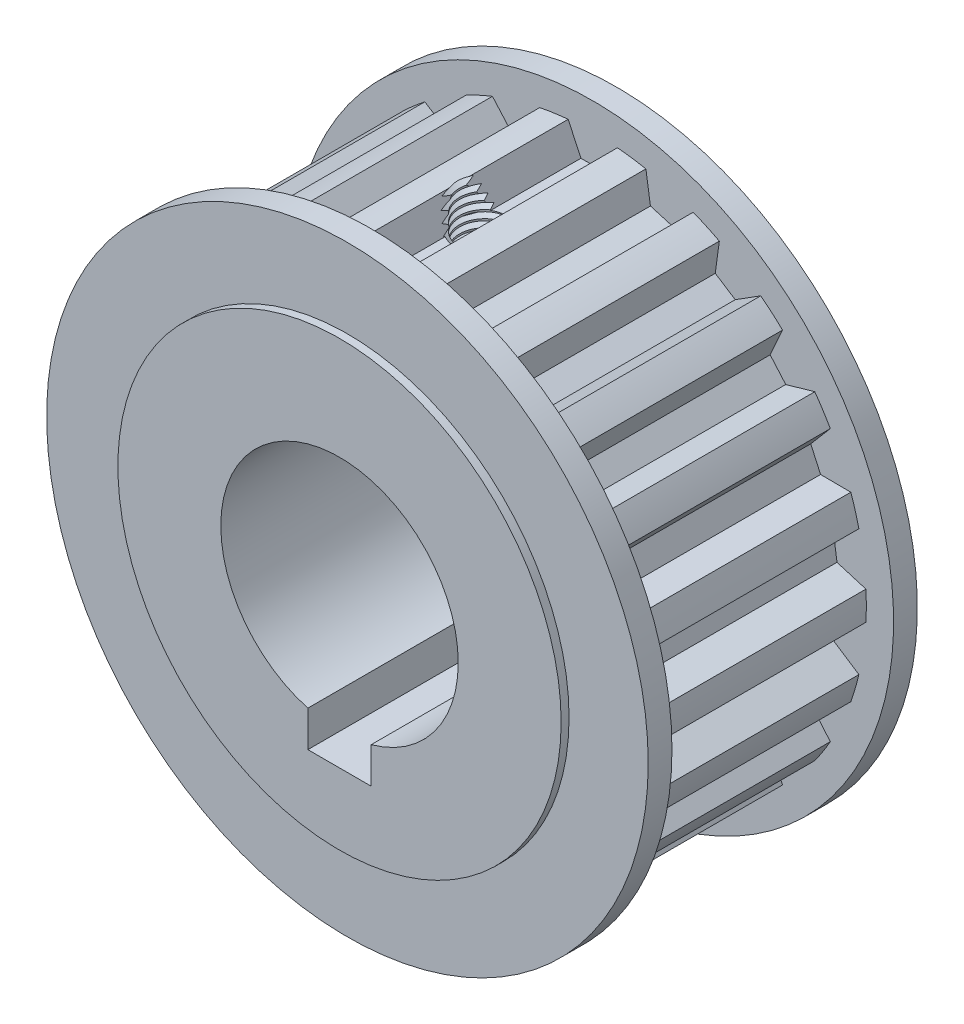
SolidWorks part; units mm, degrees
ref_plane "Front Plane" through (0, 0, 0) normal (0, 0, 1) x (1, 0, 0)
ref_plane "Top Plane" through (0, 0, 0) normal (0, 1, 0) x (1, 0, 0)
ref_plane "Right Plane" through (0, 0, 0) normal (1, 0, 0) x (0, 0, -1)
sketch "Sketch1" plane through (0, 0, 0) normal (0, 0, 1) x (1, 0, 0)
  circle A0 centre (0, 0) radius 17.275
  circle A1 centre (0, 0) radius 7.5
  dimension "D1" = 34.55
  dimension "D2" = 15
extrude "Boss-Extrude1" add sketch "Sketch1" along normal blind 18
sketch "Sketch2" plane through (0, 0, 18) normal (0, 0, 1) x (1, 0, 0)
  line L0 (0, 17.275) -> (0, 15.475) construction
  line L1 (-0.75, 15.475) -> (0.75, 15.475)
  line L2 (0.75, 15.475) -> (1.756, 17.6325)
  line L3 (-0.75, 15.475) -> (-1.756, 17.6325)
  line L4 (-1.756, 17.6325) -> (1.756, 17.6325)
  circle A0 centre (0, 0) radius 17.275 construction
  point P9 (0, 15.475)
  dimension "D1" = 1.8
  dimension "D2" = 1.5
  dimension "D3" = 25
  dimension "D4" = 25
extrude "Cut-Extrude1" cut sketch "Sketch2" against normal blind 18
pattern_circular "CirPattern1" count 22 over 360 about axis through (0, 0, 0) along (0, 0, 1) of "Cut-Extrude1"
sketch "Sketch3" plane through (0, 0, 18) normal (0, 0, 1) x (1, 0, 0)
  circle A0 centre (0, 0) radius 17.275
  circle A1 centre (0, 0) radius 14
extrude "Cut-Extrude2" cut sketch "Sketch3" against normal blind 2
sketch "Sketch4" plane through (0, 0, 0) normal (0, 0, -1) x (-1, 0, 0)
  circle A0 centre (0, 0) radius 17.275
  circle A2 centre (0, 0) radius 14
extrude "Cut-Extrude3" cut sketch "Sketch4" against normal blind 2
sketch "Sketch5" plane through (0, 0, 0) normal (0, 1, 0) x (1, 0, 0)
  line L0 (0, 0) -> (0, -18) construction
  line L1 (-14, -18) -> (14, -18) construction
  circle A0 centre (0, -9) radius 1.5
  dimension "D1" = 3
extrude "Cut-Extrude4" cut sketch "Sketch5" along normal blind 18
sketch "Sketch6" plane through (0, 0, 0) normal (0, 1, 0) x (1, 0, 0)
  line L0 (0, 0) -> (0, -18) construction
  line L1 (-14, -18) -> (14, -18) construction
  circle A0 centre (0, -9) radius 1.5
curve "Helix/Spiral1" pitch 0.5 height 20 turns 40
sketch "Sketch7" plane through (0, 0, 0) normal (1, 0, 0) x (0, 0, -1)
  line L1 (-10.8284, 19.9865) -> (-10.3034, 19.6834)
  line L2 (-10.3034, 19.6834) -> (-10.3034, 20.2896)
  line L3 (-10.3034, 20.2896) -> (-10.8284, 19.9865)
  circle A0 centre (-10.4784, 19.9865) radius 0.175 construction
  spline S0 degree 3 poles (-10.5, 0) (-10.5, 0.0104) (-10.4219, 0.0313) (-10.0883, 0.0625) (-9.589, 0.0938) (-9, 0.125) (-8.411, 0.1563) (-7.9117, 0.1875) (-7.5781, 0.2188) (-7.4609, 0.25) (-7.5781, 0.2813) (-7.9117, 0.3125) (-8.411, 0.3438) (-9, 0.375) (-9.589, 0.4063) (-10.0883, 0.4375) (-10.4219, 0.4688) (-10.5391, 0.5) (-10.4219, 0.5313) (-10.0883, 0.5625) (-9.589, 0.5938) (-9, 0.625) (-8.411, 0.6563) (-7.9117, 0.6875) (-7.5781, 0.7188) (-7.4609, 0.75) (-7.5781, 0.7813) (-7.9117, 0.8125) (-8.411, 0.8438) (-9, 0.875) (-9.589, 0.9063) (-10.0883, 0.9375) (-10.4219, 0.9688) (-10.5391, 1) (-10.4219, 1.0313) (-10.0883, 1.0625) (-9.589, 1.0938) (-9, 1.125) (-8.411, 1.1563) (-7.9117, 1.1875) (-7.5781, 1.2188) (-7.4609, 1.25) (-7.5781, 1.2813) (-7.9117, 1.3125) (-8.411, 1.3438) (-9, 1.375) (-9.589, 1.4063) (-10.0883, 1.4375) (-10.4219, 1.4688) (-10.5391, 1.5) (-10.4219, 1.5313) (-10.0883, 1.5625) (-9.589, 1.5938) (-9, 1.625) (-8.411, 1.6563) (-7.9117, 1.6875) (-7.5781, 1.7188) (-7.4609, 1.75) (-7.5781, 1.7813) (-7.9117, 1.8125) (-8.411, 1.8438) (-9, 1.875) (-9.589, 1.9063) (-10.0883, 1.9375) (-10.4219, 1.9688) (-10.5391, 2) (-10.4219, 2.0313) (-10.0883, 2.0625) (-9.589, 2.0938) (-9, 2.125) (-8.411, 2.1563) (-7.9117, 2.1875) (-7.5781, 2.2188) (-7.4609, 2.25) (-7.5781, 2.2813) (-7.9117, 2.3125) (-8.411, 2.3438) (-9, 2.375) (-9.589, 2.4063) (-10.0883, 2.4375) (-10.4219, 2.4688) (-10.5391, 2.5) (-10.4219, 2.5313) (-10.0883, 2.5625) (-9.589, 2.5938) (-9, 2.625) (-8.411, 2.6563) (-7.9117, 2.6875) (-7.5781, 2.7188) (-7.4609, 2.75) (-7.5781, 2.7813) (-7.9117, 2.8125) (-8.411, 2.8438) (-9, 2.875) (-9.589, 2.9063) (-10.0883, 2.9375) (-10.4219, 2.9688) (-10.5391, 3) (-10.4219, 3.0313) (-10.0883, 3.0625) (-9.589, 3.0938) (-9, 3.125) (-8.411, 3.1563) (-7.9117, 3.1875) (-7.5781, 3.2188) (-7.4609, 3.25) (-7.5781, 3.2813) (-7.9117, 3.3125) (-8.411, 3.3438) (-9, 3.375) (-9.589, 3.4063) (-10.0883, 3.4375) (-10.4219, 3.4688) (-10.5391, 3.5) (-10.4219, 3.5313) (-10.0883, 3.5625) (-9.589, 3.5938) (-9, 3.625) (-8.411, 3.6563) (-7.9117, 3.6875) (-7.5781, 3.7188) (-7.4609, 3.75) (-7.5781, 3.7813) (-7.9117, 3.8125) (-8.411, 3.8438) (-9, 3.875) (-9.589, 3.9063) (-10.0883, 3.9375) (-10.4219, 3.9688) (-10.5391, 4) (-10.4219, 4.0313) (-10.0883, 4.0625) (-9.589, 4.0938) (-9, 4.125) (-8.411, 4.1563) (-7.9117, 4.1875) (-7.5781, 4.2188) (-7.4609, 4.25) (-7.5781, 4.2813) (-7.9117, 4.3125) (-8.411, 4.3438) (-9, 4.375) (-9.589, 4.4063) (-10.0883, 4.4375) (-10.4219, 4.4688) (-10.5391, 4.5) (-10.4219, 4.5313) (-10.0883, 4.5625) (-9.589, 4.5938) (-9, 4.625) (-8.411, 4.6563) (-7.9117, 4.6875) (-7.5781, 4.7188) (-7.4609, 4.75) (-7.5781, 4.7813) (-7.9117, 4.8125) (-8.411, 4.8438) (-9, 4.875) (-9.589, 4.9063) (-10.0883, 4.9375) (-10.4219, 4.9688) (-10.5391, 5) (-10.4219, 5.0313) (-10.0883, 5.0625) (-9.589, 5.0938) (-9, 5.125) (-8.411, 5.1563) (-7.9117, 5.1875) (-7.5781, 5.2188) (-7.4609, 5.25) (-7.5781, 5.2813) (-7.9117, 5.3125) (-8.411, 5.3438) (-9, 5.375) (-9.589, 5.4063) (-10.0883, 5.4375) (-10.4219, 5.4688) (-10.5391, 5.5) (-10.4219, 5.5313) (-10.0883, 5.5625) (-9.589, 5.5938) (-9, 5.625) (-8.411, 5.6563) (-7.9117, 5.6875) (-7.5781, 5.7188) (-7.4609, 5.75) (-7.5781, 5.7813) (-7.9117, 5.8125) (-8.411, 5.8438) (-9, 5.875) (-9.589, 5.9063) (-10.0883, 5.9375) (-10.4219, 5.9688) (-10.5391, 6) (-10.4219, 6.0313) (-10.0883, 6.0625) (-9.589, 6.0938) (-9, 6.125) (-8.411, 6.1563) (-7.9117, 6.1875) (-7.5781, 6.2188) (-7.4609, 6.25) (-7.5781, 6.2813) (-7.9117, 6.3125) (-8.411, 6.3438) (-9, 6.375) (-9.589, 6.4063) (-10.0883, 6.4375) (-10.4219, 6.4688) (-10.5391, 6.5) (-10.4219, 6.5313) (-10.0883, 6.5625) (-9.589, 6.5938) (-9, 6.625) (-8.411, 6.6563) (-7.9117, 6.6875) (-7.5781, 6.7188) (-7.4609, 6.75) (-7.5781, 6.7813) (-7.9117, 6.8125) (-8.411, 6.8438) (-9, 6.875) (-9.589, 6.9063) (-10.0883, 6.9375) (-10.4219, 6.9688) (-10.5391, 7) (-10.4219, 7.0313) (-10.0883, 7.0625) (-9.589, 7.0938) (-9, 7.125) (-8.411, 7.1563) (-7.9117, 7.1875) (-7.5781, 7.2188) (-7.4609, 7.25) (-7.5781, 7.2813) (-7.9117, 7.3125) (-8.411, 7.3438) (-9, 7.375) (-9.589, 7.4063) (-10.0883, 7.4375) (-10.4219, 7.4688) (-10.5391, 7.5) (-10.4219, 7.5313) (-10.0883, 7.5625) (-9.589, 7.5938) (-9, 7.625) (-8.411, 7.6563) (-7.9117, 7.6875) (-7.5781, 7.7188) (-7.4609, 7.75) (-7.5781, 7.7813) (-7.9117, 7.8125) (-8.411, 7.8438) (-9, 7.875) (-9.589, 7.9063) (-10.0883, 7.9375) (-10.4219, 7.9688) (-10.5391, 8) (-10.4219, 8.0313) (-10.0883, 8.0625) (-9.589, 8.0938) (-9, 8.125) (-8.411, 8.1563) (-7.9117, 8.1875) (-7.5781, 8.2188) (-7.4609, 8.25) (-7.5781, 8.2813) (-7.9117, 8.3125) (-8.411, 8.3438) (-9, 8.375) (-9.589, 8.4063) (-10.0883, 8.4375) (-10.4219, 8.4688) (-10.5391, 8.5) (-10.4219, 8.5313) (-10.0883, 8.5625) (-9.589, 8.5938) (-9, 8.625) (-8.411, 8.6563) (-7.9117, 8.6875) (-7.5781, 8.7188) (-7.4609, 8.75) (-7.5781, 8.7813) (-7.9117, 8.8125) (-8.411, 8.8438) (-9, 8.875) (-9.589, 8.9063) (-10.0883, 8.9375) (-10.4219, 8.9688) (-10.5391, 9) (-10.4219, 9.0313) (-10.0883, 9.0625) (-9.589, 9.0938) (-9, 9.125) (-8.411, 9.1563) (-7.9117, 9.1875) (-7.5781, 9.2188) (-7.4609, 9.25) (-7.5781, 9.2813) (-7.9117, 9.3125) (-8.411, 9.3438) (-9, 9.375) (-9.589, 9.4063) (-10.0883, 9.4375) (-10.4219, 9.4688) (-10.5391, 9.5) (-10.4219, 9.5313) (-10.0883, 9.5625) (-9.589, 9.5938) (-9, 9.625) (-8.411, 9.6563) (-7.9117, 9.6875) (-7.5781, 9.7188) (-7.4609, 9.75) (-7.5781, 9.7813) (-7.9117, 9.8125) (-8.411, 9.8438) (-9, 9.875) (-9.589, 9.9063) (-10.0883, 9.9375) (-10.4219, 9.9688) (-10.5391, 10) (-10.4219, 10.0313) (-10.0883, 10.0625) (-9.589, 10.0938) (-9, 10.125) (-8.411, 10.1563) (-7.9117, 10.1875) (-7.5781, 10.2188) (-7.4609, 10.25) (-7.5781, 10.2813) (-7.9117, 10.3125) (-8.411, 10.3438) (-9, 10.375) (-9.589, 10.4063) (-10.0883, 10.4375) (-10.4219, 10.4688) (-10.5391, 10.5) (-10.4219, 10.5313) (-10.0883, 10.5625) (-9.589, 10.5938) (-9, 10.625) (-8.411, 10.6563) (-7.9117, 10.6875) (-7.5781, 10.7188) (-7.4609, 10.75) (-7.5781, 10.7813) (-7.9117, 10.8125) (-8.411, 10.8438) (-9, 10.875) (-9.589, 10.9063) (-10.0883, 10.9375) (-10.4219, 10.9688) (-10.5391, 11) (-10.4219, 11.0313) (-10.0883, 11.0625) (-9.589, 11.0938) (-9, 11.125) (-8.411, 11.1563) (-7.9117, 11.1875) (-7.5781, 11.2188) (-7.4609, 11.25) (-7.5781, 11.2813) (-7.9117, 11.3125) (-8.411, 11.3438) (-9, 11.375) (-9.589, 11.4063) (-10.0883, 11.4375) (-10.4219, 11.4688) (-10.5391, 11.5) (-10.4219, 11.5313) (-10.0883, 11.5625) (-9.589, 11.5938) (-9, 11.625) (-8.411, 11.6563) (-7.9117, 11.6875) (-7.5781, 11.7188) (-7.4609, 11.75) (-7.5781, 11.7813) (-7.9117, 11.8125) (-8.411, 11.8438) (-9, 11.875) (-9.589, 11.9063) (-10.0883, 11.9375) (-10.4219, 11.9688) (-10.5391, 12) (-10.4219, 12.0313) (-10.0883, 12.0625) (-9.589, 12.0938) (-9, 12.125) (-8.411, 12.1563) (-7.9117, 12.1875) (-7.5781, 12.2188) (-7.4609, 12.25) (-7.5781, 12.2813) (-7.9117, 12.3125) (-8.411, 12.3438) (-9, 12.375) (-9.589, 12.4063) (-10.0883, 12.4375) (-10.4219, 12.4688) (-10.5391, 12.5) (-10.4219, 12.5313) (-10.0883, 12.5625) (-9.589, 12.5938) (-9, 12.625) (-8.411, 12.6563) (-7.9117, 12.6875) (-7.5781, 12.7188) (-7.4609, 12.75) (-7.5781, 12.7813) (-7.9117, 12.8125) (-8.411, 12.8438) (-9, 12.875) (-9.589, 12.9063) (-10.0883, 12.9375) (-10.4219, 12.9688) (-10.5391, 13) (-10.4219, 13.0313) (-10.0883, 13.0625) (-9.589, 13.0938) (-9, 13.125) (-8.411, 13.1563) (-7.9117, 13.1875) (-7.5781, 13.2188) (-7.4609, 13.25) (-7.5781, 13.2813) (-7.9117, 13.3125) (-8.411, 13.3438) (-9, 13.375) (-9.589, 13.4063) (-10.0883, 13.4375) (-10.4219, 13.4688) (-10.5391, 13.5) (-10.4219, 13.5313) (-10.0883, 13.5625) (-9.589, 13.5938) (-9, 13.625) (-8.411, 13.6563) (-7.9117, 13.6875) (-7.5781, 13.7188) (-7.4609, 13.75) (-7.5781, 13.7813) (-7.9117, 13.8125) (-8.411, 13.8438) (-9, 13.875) (-9.589, 13.9063) (-10.0883, 13.9375) (-10.4219, 13.9688) (-10.5391, 14) (-10.4219, 14.0313) (-10.0883, 14.0625) (-9.589, 14.0938) (-9, 14.125) (-8.411, 14.1563) (-7.9117, 14.1875) (-7.5781, 14.2188) (-7.4609, 14.25) (-7.5781, 14.2813) (-7.9117, 14.3125) (-8.411, 14.3438) (-9, 14.375) (-9.589, 14.4063) (-10.0883, 14.4375) (-10.4219, 14.4688) (-10.5391, 14.5) (-10.4219, 14.5313) (-10.0883, 14.5625) (-9.589, 14.5938) (-9, 14.625) (-8.411, 14.6563) (-7.9117, 14.6875) (-7.5781, 14.7188) (-7.4609, 14.75) (-7.5781, 14.7813) (-7.9117, 14.8125) (-8.411, 14.8438) (-9, 14.875) (-9.589, 14.9063) (-10.0883, 14.9375) (-10.4219, 14.9688) (-10.5391, 15) (-10.4219, 15.0313) (-10.0883, 15.0625) (-9.589, 15.0938) (-9, 15.125) (-8.411, 15.1563) (-7.9117, 15.1875) (-7.5781, 15.2188) (-7.4609, 15.25) (-7.5781, 15.2813) (-7.9117, 15.3125) (-8.411, 15.3438) (-9, 15.375) (-9.589, 15.4063) (-10.0883, 15.4375) (-10.4219, 15.4688) (-10.5391, 15.5) (-10.4219, 15.5313) (-10.0883, 15.5625) (-9.589, 15.5938) (-9, 15.625) (-8.411, 15.6563) (-7.9117, 15.6875) (-7.5781, 15.7188) (-7.4609, 15.75) (-7.5781, 15.7813) (-7.9117, 15.8125) (-8.411, 15.8438) (-9, 15.875) (-9.589, 15.9063) (-10.0883, 15.9375) (-10.4219, 15.9688) (-10.5391, 16) (-10.4219, 16.0313) (-10.0883, 16.0625) (-9.589, 16.0938) (-9, 16.125) (-8.411, 16.1563) (-7.9117, 16.1875) (-7.5781, 16.2188) (-7.4609, 16.25) (-7.5781, 16.2813) (-7.9117, 16.3125) (-8.411, 16.3438) (-9, 16.375) (-9.589, 16.4063) (-10.0883, 16.4375) (-10.4219, 16.4688) (-10.5391, 16.5) (-10.4219, 16.5313) (-10.0883, 16.5625) (-9.589, 16.5938) (-9, 16.625) (-8.411, 16.6563) (-7.9117, 16.6875) (-7.5781, 16.7188) (-7.4609, 16.75) (-7.5781, 16.7813) (-7.9117, 16.8125) (-8.411, 16.8438) (-9, 16.875) (-9.589, 16.9063) (-10.0883, 16.9375) (-10.4219, 16.9688) (-10.5391, 17) (-10.4219, 17.0313) (-10.0883, 17.0625) (-9.589, 17.0938) (-9, 17.125) (-8.411, 17.1563) (-7.9117, 17.1875) (-7.5781, 17.2188) (-7.4609, 17.25) (-7.5781, 17.2813) (-7.9117, 17.3125) (-8.411, 17.3438) (-9, 17.375) (-9.589, 17.4063) (-10.0883, 17.4375) (-10.4219, 17.4688) (-10.5391, 17.5) (-10.4219, 17.5313) (-10.0883, 17.5625) (-9.589, 17.5938) (-9, 17.625) (-8.411, 17.6563) (-7.9117, 17.6875) (-7.5781, 17.7188) (-7.4609, 17.75) (-7.5781, 17.7813) (-7.9117, 17.8125) (-8.411, 17.8438) (-9, 17.875) (-9.589, 17.9063) (-10.0883, 17.9375) (-10.4219, 17.9688) (-10.5391, 18) (-10.4219, 18.0313) (-10.0883, 18.0625) (-9.589, 18.0938) (-9, 18.125) (-8.411, 18.1563) (-7.9117, 18.1875) (-7.5781, 18.2188) (-7.4609, 18.25) (-7.5781, 18.2813) (-7.9117, 18.3125) (-8.411, 18.3438) (-9, 18.375) (-9.589, 18.4063) (-10.0883, 18.4375) (-10.4219, 18.4688) (-10.5391, 18.5) (-10.4219, 18.5313) (-10.0883, 18.5625) (-9.589, 18.5938) (-9, 18.625) (-8.411, 18.6563) (-7.9117, 18.6875) (-7.5781, 18.7188) (-7.4609, 18.75) (-7.5781, 18.7813) (-7.9117, 18.8125) (-8.411, 18.8438) (-9, 18.875) (-9.589, 18.9063) (-10.0883, 18.9375) (-10.4219, 18.9688) (-10.5391, 19) (-10.4219, 19.0313) (-10.0883, 19.0625) (-9.589, 19.0938) (-9, 19.125) (-8.411, 19.1563) (-7.9117, 19.1875) (-7.5781, 19.2188) (-7.4609, 19.25) (-7.5781, 19.2813) (-7.9117, 19.3125) (-8.411, 19.3438) (-9, 19.375) (-9.589, 19.4063) (-10.0883, 19.4375) (-10.4219, 19.4687) (-10.5391, 19.5) (-10.4219, 19.5312) (-10.0883, 19.5625) (-9.589, 19.5937) (-9, 19.625) (-8.411, 19.6562) (-7.9117, 19.6875) (-7.5781, 19.7187) (-7.4609, 19.75) (-7.5781, 19.7812) (-7.9117, 19.8125) (-8.411, 19.8437) (-9, 19.875) (-9.589, 19.9062) (-10.0883, 19.9375) (-10.4219, 19.9687) (-10.5, 19.9896) (-10.5, 20) knots 0 0 0 0 0.001563 0.003125 0.004688 0.00625 0.007813 0.009375 0.010938 0.0125 0.014063 0.015625 0.017188 0.01875 0.020313 0.021875 0.023438 0.025 0.026563 0.028125 0.029688 0.03125 0.032813 0.034375 0.035938 0.0375 0.039063 0.040625 0.042188 0.04375 0.045313 0.046875 0.048438 0.05 0.051563 0.053125 0.054688 0.05625 0.057813 0.059375 0.060938 0.0625 0.064063 0.065625 0.067188 0.06875 0.070313 0.071875 0.073438 0.075 0.076563 0.078125 0.079688 0.08125 0.082813 0.084375 0.085938 0.0875 0.089063 0.090625 0.092188 0.09375 0.095313 0.096875 0.098438 0.1 0.101563 0.103125 0.104688 0.10625 0.107813 0.109375 0.110938 0.1125 0.114063 0.115625 0.117188 0.11875 0.120313 0.121875 0.123438 0.125 0.126563 0.128125 0.129688 0.13125 0.132813 0.134375 0.135938 0.1375 0.139063 0.140625 0.142188 0.14375 0.145313 0.146875 0.148438 0.15 0.151563 0.153125 0.154688 0.15625 0.157813 0.159375 0.160938 0.1625 0.164063 0.165625 0.167188 0.16875 0.170313 0.171875 0.173438 0.175 0.176563 0.178125 0.179688 0.18125 0.182813 0.184375 0.185938 0.1875 0.189063 0.190625 0.192188 0.19375 0.195313 0.196875 0.198438 0.2 0.201563 0.203125 0.204688 0.20625 0.207813 0.209375 0.210938 0.2125 0.214063 0.215625 0.217188 0.21875 0.220313 0.221875 0.223438 0.225 0.226563 0.228125 0.229688 0.23125 0.232813 0.234375 0.235938 0.2375 0.239063 0.240625 0.242188 0.24375 0.245313 0.246875 0.248438 0.25 0.251563 0.253125 0.254688 0.25625 0.257813 0.259375 0.260938 0.2625 0.264063 0.265625 0.267188 0.26875 0.270313 0.271875 0.273438 0.275 0.276563 0.278125 0.279688 0.28125 0.282813 0.284375 0.285938 0.2875 0.289063 0.290625 0.292188 0.29375 0.295313 0.296875 0.298438 0.3 0.301563 0.303125 0.304688 0.30625 0.307813 0.309375 0.310938 0.3125 0.314063 0.315625 0.317188 0.31875 0.320313 0.321875 0.323438 0.325 0.326563 0.328125 0.329688 0.33125 0.332813 0.334375 0.335938 0.3375 0.339063 0.340625 0.342188 0.34375 0.345313 0.346875 0.348438 0.35 0.351563 0.353125 0.354688 0.35625 0.357813 0.359375 0.360938 0.3625 0.364063 0.365625 0.367188 0.36875 0.370313 0.371875 0.373438 0.375 0.376563 0.378125 0.379688 0.38125 0.382813 0.384375 0.385938 0.3875 0.389063 0.390625 0.392188 0.39375 0.395313 0.396875 0.398438 0.4 0.401563 0.403125 0.404688 0.40625 0.407813 0.409375 0.410938 0.4125 0.414063 0.415625 0.417188 0.41875 0.420313 0.421875 0.423438 0.425 0.426563 0.428125 0.429688 0.43125 0.432813 0.434375 0.435938 0.4375 0.439063 0.440625 0.442188 0.44375 0.445313 0.446875 0.448438 0.45 0.451563 0.453125 0.454688 0.45625 0.457813 0.459375 0.460938 0.4625 0.464063 0.465625 0.467188 0.46875 0.470313 0.471875 0.473438 0.475 0.476563 0.478125 0.479688 0.48125 0.482813 0.484375 0.485938 0.4875 0.489063 0.490625 0.492188 0.49375 0.495313 0.496875 0.498438 0.5 0.501563 0.503125 0.504688 0.50625 0.507813 0.509375 0.510938 0.5125 0.514063 0.515625 0.517188 0.51875 0.520313 0.521875 0.523438 0.525 0.526563 0.528125 0.529688 0.53125 0.532813 0.534375 0.535938 0.5375 0.539063 0.540625 0.542188 0.54375 0.545313 0.546875 0.548438 0.55 0.551563 0.553125 0.554688 0.55625 0.557813 0.559375 0.560938 0.5625 0.564063 0.565625 0.567188 0.56875 0.570313 0.571875 0.573438 0.575 0.576563 0.578125 0.579688 0.58125 0.582813 0.584375 0.585938 0.5875 0.589063 0.590625 0.592188 0.59375 0.595313 0.596875 0.598438 0.6 0.601563 0.603125 0.604688 0.60625 0.607813 0.609375 0.610938 0.6125 0.614063 0.615625 0.617188 0.61875 0.620313 0.621875 0.623438 0.625 0.626563 0.628125 0.629688 0.63125 0.632813 0.634375 0.635938 0.6375 0.639063 0.640625 0.642188 0.64375 0.645313 0.646875 0.648438 0.65 0.651563 0.653125 0.654688 0.65625 0.657813 0.659375 0.660938 0.6625 0.664063 0.665625 0.667188 0.66875 0.670313 0.671875 0.673438 0.675 0.676563 0.678125 0.679688 0.68125 0.682813 0.684375 0.685938 0.6875 0.689063 0.690625 0.692188 0.69375 0.695313 0.696875 0.698438 0.7 0.701563 0.703125 0.704688 0.70625 0.707813 0.709375 0.710938 0.7125 0.714063 0.715625 0.717188 0.71875 0.720313 0.721875 0.723438 0.725 0.726563 0.728125 0.729688 0.73125 0.732813 0.734375 0.735938 0.7375 0.739063 0.740625 0.742188 0.74375 0.745313 0.746875 0.748438 0.75 0.751563 0.753125 0.754688 0.75625 0.757813 0.759375 0.760938 0.7625 0.764063 0.765625 0.767188 0.76875 0.770313 0.771875 0.773438 0.775 0.776563 0.778125 0.779688 0.78125 0.782813 0.784375 0.785938 0.7875 0.789063 0.790625 0.792188 0.79375 0.795313 0.796875 0.798438 0.8 0.801563 0.803125 0.804688 0.80625 0.807813 0.809375 0.810938 0.8125 0.814063 0.815625 0.817188 0.81875 0.820313 0.821875 0.823438 0.825 0.826563 0.828125 0.829688 0.83125 0.832813 0.834375 0.835938 0.8375 0.839063 0.840625 0.842188 0.84375 0.845313 0.846875 0.848438 0.85 0.851563 0.853125 0.854688 0.85625 0.857813 0.859375 0.860938 0.8625 0.864063 0.865625 0.867188 0.86875 0.870313 0.871875 0.873438 0.875 0.876563 0.878125 0.879688 0.88125 0.882813 0.884375 0.885938 0.8875 0.889063 0.890625 0.892188 0.89375 0.895313 0.896875 0.898438 0.9 0.901563 0.903125 0.904688 0.90625 0.907813 0.909375 0.910938 0.9125 0.914063 0.915625 0.917188 0.91875 0.920313 0.921875 0.923438 0.925 0.926563 0.928125 0.929688 0.93125 0.932813 0.934375 0.935938 0.9375 0.939063 0.940625 0.942188 0.94375 0.945313 0.946875 0.948438 0.95 0.951563 0.953125 0.954688 0.95625 0.957813 0.959375 0.960938 0.9625 0.964063 0.965625 0.967188 0.96875 0.970313 0.971875 0.973438 0.975 0.976563 0.978125 0.979688 0.98125 0.982813 0.984375 0.985938 0.9875 0.989063 0.990625 0.992188 0.99375 0.995313 0.996875 0.998438 1 1 1 1 construction
sweep "Cut-Sweep1" cut profiles "Sketch7" path "Helix/Spiral1"
sketch "Sketch8" plane through (0, 0, 2) normal (0, 0, -1) x (-1, 0, 0)
  circle A0 centre (0, 0) radius 19
  circle A1 centre (0, 0) radius 14
  dimension "D1" = 38
extrude "Boss-Extrude2" add sketch "Sketch8" along normal blind 1.5
sketch "Sketch9" plane through (0, 0, 16) normal (0, 0, 1) x (1, 0, 0)
  circle A0 centre (0, 0) radius 19
  circle A1 centre (0, 0) radius 14
extrude "Boss-Extrude3" add sketch "Sketch9" along normal blind 1.5
sketch "Sketch10" plane through (0, 0, 18) normal (0, 0, 1) x (1, 0, 0)
  line L1 (-2, -5.5) -> (2, -5.5)
  line L2 (-2, -5.5) -> (-2, -9.5)
  line L3 (-2, -9.5) -> (2, -9.5)
  line L4 (2, -5.5) -> (2, -9.5)
  line L5 (-2, -5.5) -> (2, -9.5) construction
  line L6 (-2, -9.5) -> (2, -5.5) construction
  circle A0 centre (0, 0) radius 7.5 construction
  point P0 (0, -7.5)
  dimension "D1" = 4
  dimension "D2" = 4
extrude "Cut-Extrude5" cut sketch "Sketch10" against normal through all
